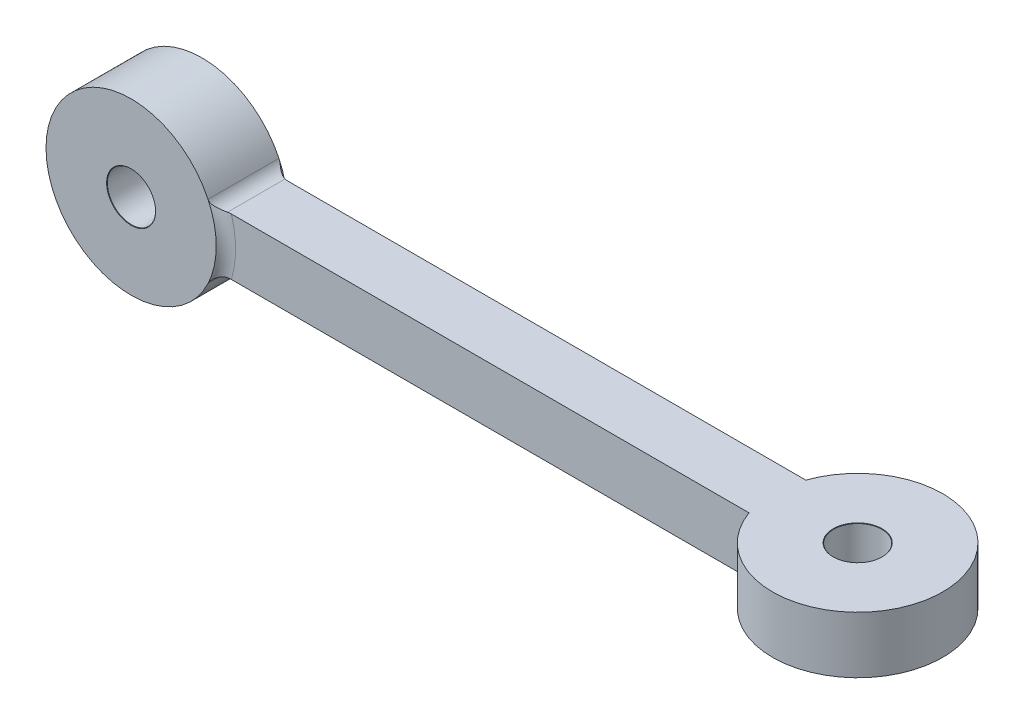
SolidWorks part; units mm, degrees
ref_plane "Front Plane" through (0, 0, 0) normal (0, 0, 1) x (1, 0, 0)
ref_plane "Top Plane" through (0, 0, 0) normal (0, 1, 0) x (1, 0, 0)
ref_plane "Right Plane" through (0, 0, 0) normal (1, 0, 0) x (0, 0, -1)
sketch "Sketch4" plane through (0, 0, 0) normal (0, 1, 0) x (1, 0, 0)
  line L1 (0, 0) -> (45.7195, 0)
  line L2 (0, 0) -> (0, 4)
  line L3 (0, 4) -> (45.7195, 4)
  line L4 (45.7195, 0) -> (45.7195, 4)
  circle A1 centre (45.7195, 2) radius 6
  point P5 (0, 0)
  dimension "D1" = 4
  dimension "D2" = 12
ref_plane "Plane2" through (0, 0, -2) normal (0, 0, 1) x (1, 0, 0)
sketch "Sketch7" plane through (0, 0, -2) normal (0, 0, 1) x (1, 0, 0)
  circle A1 centre (-3, 0) radius 6
  dimension "D2" = 12
extrude "Boss-Extrude10" add sketch "Sketch7" along normal blind 2.5 and the other way blind 2.5 contours A1
extrude "Boss-Extrude11" add sketch "Sketch4" along normal blind 2 and the other way blind 2 contours L1 A1 L3 L4 | L3 A1 L1 L4 | A1 L3 L2 L1 region at (19.9164, 0, -2) region at (42.7752, 0, -2) region at (46.4938, 0, -2)
fillet "Fillet4" radius 1 4 edges at (2.6569, -2, -2) (3, 0, -4) (2.6569, 2, -2) (3, 0, 0)
hole_wizard "M3 Clearance Hole1" positions "Sketch8" profile "Sketch9" hole size "M3" standard "ANSI Metric" end condition through all
sketch "Sketch8" plane through (0, 0, 0.5) normal (0, 0, 1) x (1, 0, 0)
  point P0 (-3, 0)
sketch "Sketch9" plane through (-3, 0, 0.5) normal (1, 0, 0) x (0, -1, 0)
  line L0 (0, 0) -> (0, 8.5)
  line L1 (0, 8.5) -> (1.7, 8.5)
  line L2 (1.7, 8.5) -> (1.7, 0.025)
  line L3 (1.7, 0.025) -> (1.725, 0)
  line L5 (1.725, 0) -> (0, 0)
  line L6 (-1.7, 0.025) -> (-1.725, 0) construction
  line L11 (0, -6.35) -> (0, 107.95) construction
  dimension "Thru Hole Dia." = 3.4
  dimension "Thru Hole Depth" = 8.5
  dimension "Near C'Sink Dia." = 3.45
  dimension "Near C'Sink Angle" = 90
hole_wizard "M3 Clearance Hole2" positions "Sketch12" profile "Sketch13" hole size "M3" standard "ANSI Metric" end condition through all
sketch "Sketch12" plane through (0, 2, 0) normal (0, 1, 0) x (1, 0, 0)
  point P0 (45.7195, 2)
sketch "Sketch13" plane through (45.7195, 2, -2) normal (1, 0, 0) x (0, 0, 1)
  line L0 (0, 0) -> (0, 8)
  line L1 (0, 8) -> (1.7, 8)
  line L2 (1.7, 8) -> (1.7, 0.025)
  line L3 (1.7, 0.025) -> (1.725, 0)
  line L5 (1.725, 0) -> (0, 0)
  line L6 (-1.7, 0.025) -> (-1.725, 0) construction
  line L11 (0, -6.35) -> (0, 107.95) construction
  dimension "Thru Hole Dia." = 3.4
  dimension "Thru Hole Depth" = 8
  dimension "Near C'Sink Dia." = 3.45
  dimension "Near C'Sink Angle" = 90
